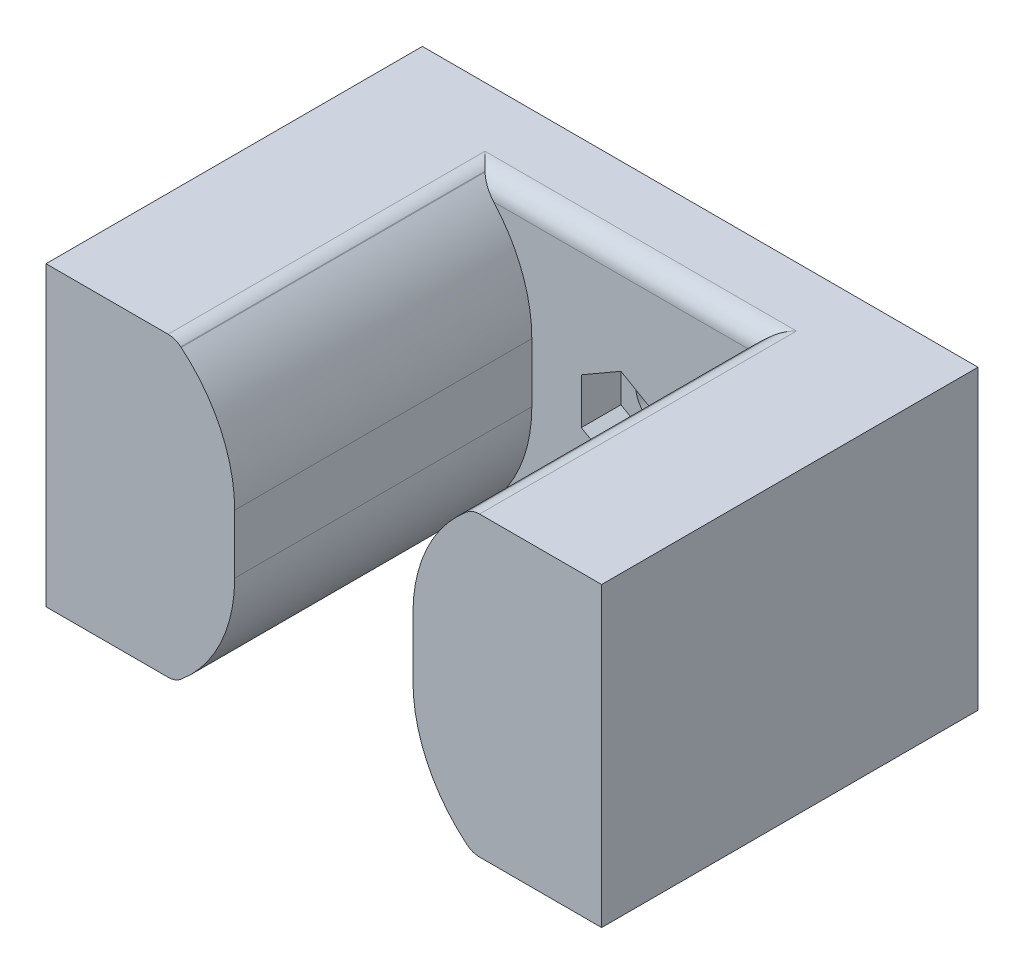
SolidWorks part; units mm, degrees
ref_plane "Спереди" through (0, 0, 0) normal (0, 0, 1) x (1, 0, 0)
ref_plane "Сверху" through (0, 0, 0) normal (0, 1, 0) x (1, 0, 0)
ref_plane "Справа" through (0, 0, 0) normal (1, 0, 0) x (0, 0, -1)
sketch "Эскиз1" plane through (0, 0, 0) normal (0, 0, 1) x (1, 0, 0)
  line L1 (0, 0) -> (56.1, 0)
  line L2 (0, 0) -> (0, 30)
  line L3 (0, 30) -> (56.1, 30)
  line L4 (56.1, 0) -> (56.1, 30)
  dimension "D1" = 56.1
  dimension "D2" = 30
extrude "Бобышка-Вытянуть1" add sketch "Эскиз1" along normal blind 8 contours L1 L4 L3 L2
sketch "Эскиз2" plane through (0, 0, 8) normal (0, 0, 1) x (1, 0, 0)
  line L0 (19.05, 17.9744) -> (19.05, 12.0256)
  line L1 (13.6528, 0.5023) -> (13.05, 0)
  line L2 (28.05, 30) -> (28.05, 0) construction
  line L3 (37.05, 17.9744) -> (37.05, 12.0256)
  line L4 (0, 30) -> (0, 0)
  line L5 (0, 0) -> (56.1, 0)
  line L6 (56.1, 0) -> (56.1, 30)
  line L7 (56.1, 30) -> (0, 30)
  line L8 (0, 30) -> (0, 0)
  line L9 (0, 0) -> (56.1, 0)
  line L10 (56.1, 0) -> (56.1, 30)
  line L11 (56.1, 30) -> (0, 30)
  line L12 (42.4472, 0.5023) -> (43.05, 0)
  line L13 (13.05, 0) -> (43.05, 0)
  line L14 (19.05, 30) -> (37.05, 30)
  line L15 (13.05, 30) -> (13.6528, 29.4977)
  line L16 (43.05, 30) -> (42.4472, 29.4977)
  arc A0 (13.6528, 0.5023) -> (19.05, 12.0256) centre (4.05, 12.0256) ccw
  arc A1 (42.4472, 0.5023) -> (37.05, 12.0256) centre (52.05, 12.0256) cw
  arc A2 (37.05, 17.9744) -> (42.4472, 29.4977) centre (52.05, 17.9744) cw
  arc A3 (19.05, 17.9744) -> (13.6528, 29.4977) centre (4.05, 17.9744) ccw
  point P15 (19.05, 5)
  point P18 (37.05, 5)
  point P24 (37.05, 25)
  point P27 (19.05, 25)
  line M7 (0, 30) -> (0, 0)
  line M8 (0, 0) -> (56.1, 0)
  line M9 (56.1, 0) -> (56.1, 30)
  line M10 (56.1, 30) -> (0, 30)
  dimension "D5" = 15
  dimension "D8" = 15
  dimension "D2" = 5
  dimension "D3" = 18
  dimension "D4" = 30
  dimension "D6" = 5
  dimension "D7" = 9
  dimension "D1" = 0
extrude "Бобышка-Вытянуть2" add sketch "Эскиз2" along normal blind 30 contours L1 A0 L0 M10 M7 M8 | A1 L12 L9 L3 M9 M10 region at (8.8798, 15, 8) region at (47.2202, 15, 8)
fillet "Скругление1" radius 2 6 edges at (28.05, 0, 8) (43.05, 0, 23) (13.05, 0, 23) (28.05, 30, 8) (43.05, 30, 23) (13.05, 30, 23)
sketch "Эскиз5" plane through (0, 0, 8) normal (0, 0, 1) x (1, 0, 0)
  line L0 (19.05, 15) -> (37.05, 15) construction
  line L1 (19.05, 17.9744) -> (19.05, 12.0256) construction
  line L2 (37.05, 17.9744) -> (37.05, 12.0256) construction
  line L4 (28.05, 10.3812) -> (32.05, 12.6906)
  line L5 (32.05, 12.6906) -> (32.05, 17.3094)
  line L6 (32.05, 17.3094) -> (28.05, 19.6188)
  line L7 (28.05, 19.6188) -> (24.05, 17.3094)
  line L8 (24.05, 17.3094) -> (24.05, 12.6906)
  line L9 (24.05, 12.6906) -> (28.05, 10.3812)
  circle A0 centre (28.05, 15) radius 4 construction
  dimension "D1" = 8
extrude "Вырез-Вытянуть1" cut sketch "Эскиз5" against normal blind 4 contours L7 L8 L9 L4 L5 L6
sketch "Эскиз6" plane through (0, 0, 4) normal (0, 0, 1) x (1, 0, 0)
  line L0 (28.05, 19.6188) -> (28.05, 10.3812) construction
  circle A0 centre (28.05, 15) radius 2.5
  point P2 (30.5161, 15.9596)
  point P7 (28.05, 15)
  dimension "D1" = 5
extrude "Вырез-Вытянуть2" cut sketch "Эскиз6" against normal up to next contours A0
